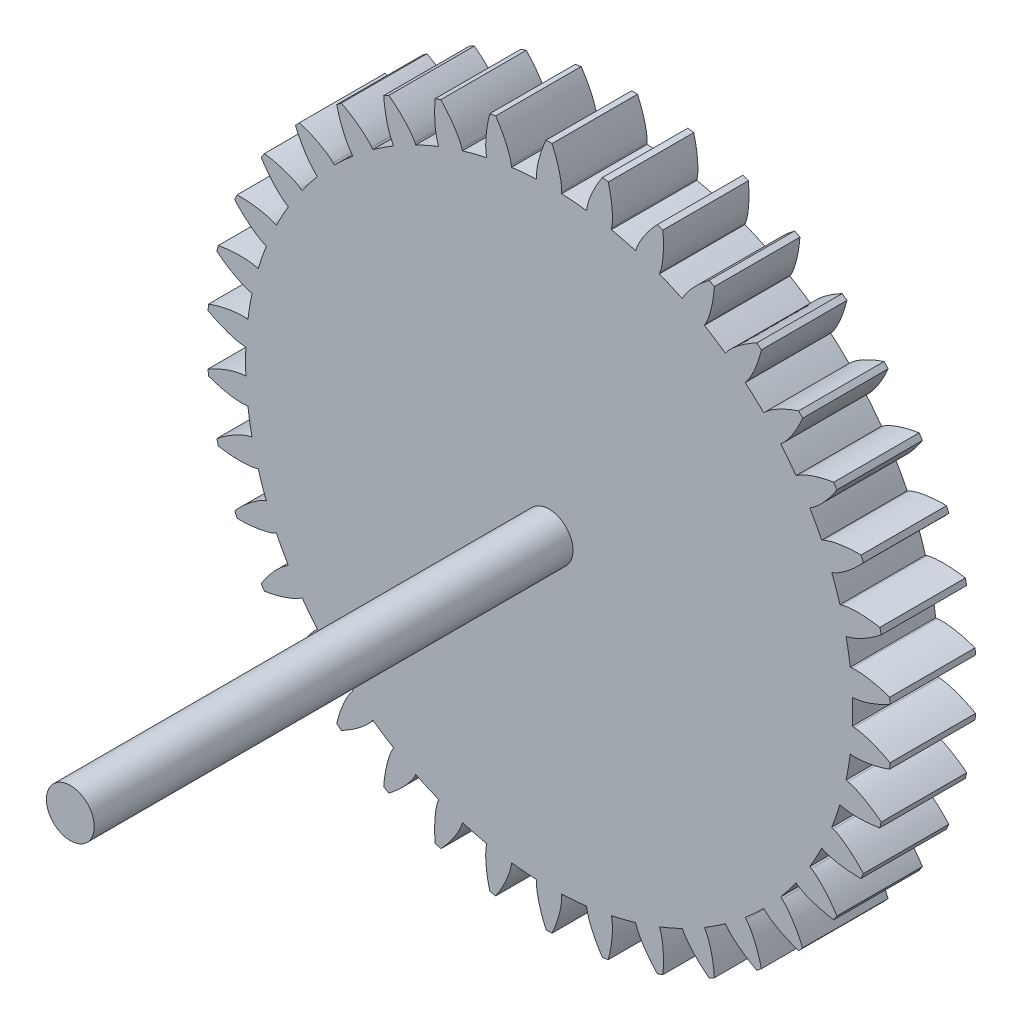
SolidWorks part; units mm, degrees
ref_plane "前视基准面" through (0, 0, 0) normal (0, 0, 1) x (1, 0, 0)
ref_plane "上视基准面" through (0, 0, 0) normal (0, 1, 0) x (1, 0, 0)
ref_plane "右视基准面" through (0, 0, 0) normal (1, 0, 0) x (0, 0, -1)
other "Configuration Table"
sketch "草图1" plane through (0, 0, 0) normal (0, 0, 1) x (1, 0, 0)
  line L0 (0, 0) -> (3, 0) construction
  line L1 (0, 0) -> (2.8978, 0.7765) construction
  line L2 (0, 0) -> (2.7305, 0.701)
  line L3 (2.8978, 0.7765) -> (2.8978, -0.7765) construction
  line L4 (0, 0) -> (2.7305, -0.701)
  circle A0 centre (0, 0) radius 4
  circle A1 centre (0, 0) radius 3 construction
  circle A2 centre (0, 0) radius 1.75
  circle A3 centre (0, 0) radius 2.8191 construction
  circle A4 centre (0, 0) radius 1.4
  spline S0 degree 4 poles (2.7305, 0.701) (2.7514, 0.7063) (2.8083, 0.7255) (2.9105, 0.779) (3.0627, 0.8875) (3.236, 1.0573) (3.4253, 1.3046) (3.6012, 1.6247) (3.742, 2.0003) (3.8364, 2.4221) (3.8779, 2.852) (3.8707, 3.2837) (3.8157, 3.7334) (3.69, 4.2802) (3.4574, 4.9086) (3.0836, 5.5918) (2.5556, 6.2772) (1.9356, 6.8796) (1.2391, 7.3923) (0.4849, 7.8122) (-0.3175, 8.1368) (-1.1468, 8.3674) (-2.0054, 8.5023) (-2.7502, 8.5427) (-3.4127, 8.5171) (-3.8849, 8.4708) (-4.3024, 8.4076) (-4.5772, 8.3558) (-4.9624, 8.2714) (-5.2496, 8.1908) (-5.5362, 8.1071) (-5.6783, 8.056) (-5.7704, 8.0254) knots 0 0 0 0 0 0.005604 0.015718 0.02996 0.048734 0.068727 0.096889 0.125051 0.153212 0.181374 0.209535 0.237696 0.271429 0.327752 0.384075 0.440398 0.496721 0.553044 0.609367 0.66569 0.722013 0.778336 0.834659 0.86282 0.890982 0.909091 0.931818 0.954545 0.977273 1 1 1 1 1 construction
  spline S1 degree 4 poles (2.7305, 0.701) (2.7514, 0.7063) (2.8083, 0.7255) (2.9105, 0.779) (3.0627, 0.8875) (3.236, 1.0573) (3.4253, 1.3046) (3.6012, 1.6247) (3.742, 2.0003) (3.8364, 2.4221) (3.8779, 2.852) (3.8707, 3.2837) (3.8157, 3.7334) (3.69, 4.2802) (3.4574, 4.9086) (3.0836, 5.5918) (2.5556, 6.2772) (1.9356, 6.8796) (1.2391, 7.3923) (0.4849, 7.8122) (-0.3175, 8.1368) (-1.1468, 8.3674) (-2.0054, 8.5023) (-2.7502, 8.5427) (-3.4127, 8.5171) (-3.8849, 8.4708) (-4.2047, 8.4224) (-4.3632, 8.395) (-4.4251, 8.3835) knots 0 0 0 0 0 0.005604 0.015718 0.02996 0.048734 0.068727 0.096889 0.125051 0.153212 0.181374 0.209535 0.237696 0.271429 0.327752 0.384075 0.440398 0.496721 0.553044 0.609367 0.66569 0.722013 0.778336 0.834659 0.86282 0.890982 0.909091 0.909091 0.909091 0.909091 0.909091
  spline S2 degree 4 poles (2.7305, -0.701) (2.7514, -0.7063) (2.8083, -0.7255) (2.9105, -0.779) (3.0627, -0.8875) (3.236, -1.0573) (3.4253, -1.3046) (3.6012, -1.6247) (3.742, -2.0003) (3.8364, -2.4221) (3.8779, -2.852) (3.8707, -3.2837) (3.8157, -3.7334) (3.69, -4.2802) (3.4574, -4.9086) (3.0836, -5.5918) (2.5556, -6.2772) (1.9356, -6.8796) (1.2391, -7.3923) (0.4849, -7.8122) (-0.3175, -8.1368) (-1.1468, -8.3674) (-2.0054, -8.5023) (-2.7502, -8.5427) (-3.4127, -8.5171) (-3.8849, -8.4708) (-4.3024, -8.4076) (-4.5772, -8.3558) (-4.9624, -8.2714) (-5.2496, -8.1908) (-5.5362, -8.1071) (-5.6783, -8.056) (-5.7704, -8.0254) knots 0 0 0 0 0 0.005604 0.015718 0.02996 0.048734 0.068727 0.096889 0.125051 0.153212 0.181374 0.209535 0.237696 0.271429 0.327752 0.384075 0.440398 0.496721 0.553044 0.609367 0.66569 0.722013 0.778336 0.834659 0.86282 0.890982 0.909091 0.931818 0.954545 0.977273 1 1 1 1 1 construction
  spline S3 degree 4 poles (2.7305, -0.701) (2.7514, -0.7063) (2.8083, -0.7255) (2.9105, -0.779) (3.0627, -0.8875) (3.236, -1.0573) (3.4253, -1.3046) (3.6012, -1.6247) (3.742, -2.0003) (3.8364, -2.4221) (3.8779, -2.852) (3.8707, -3.2837) (3.8157, -3.7334) (3.69, -4.2802) (3.4574, -4.9086) (3.0836, -5.5918) (2.5556, -6.2772) (1.9356, -6.8796) (1.2391, -7.3923) (0.4849, -7.8122) (-0.3175, -8.1368) (-1.1468, -8.3674) (-2.0054, -8.5023) (-2.7502, -8.5427) (-3.4127, -8.5171) (-3.8849, -8.4708) (-4.2047, -8.4224) (-4.3632, -8.395) (-4.4251, -8.3835) knots 0 0 0 0 0 0.005604 0.015718 0.02996 0.048734 0.068727 0.096889 0.125051 0.153212 0.181374 0.209535 0.237696 0.271429 0.327752 0.384075 0.440398 0.496721 0.553044 0.609367 0.66569 0.722013 0.778336 0.834659 0.86282 0.890982 0.909091 0.909091 0.909091 0.909091 0.909091
  point P15 (2.8978, 0)
  dimension "齿顶圆直径" = 8
  dimension "分度圆直径" = 6
  dimension "齿根圆直径" = 3.5
  dimension "基圆直径" = 5.6382
  dimension "内孔直径" = 2.8
  dimension "渐近线镜像线夹角" = 15
extrude "凸台-拉伸1" add sketch "草图1" along normal blind 5 contours A0 | A4
extrude "切除-拉伸1" cut sketch "草图1<3>" along normal through all contours A2 S3 A0 S1 region at (3.0753, 0, 0)
sketch "草图1<3>" plane through (0, 0, 0) normal (0, 0, 1) x (1, 0, 0) same geometry as "草图1"
pattern_circular "阵列(圆周)1" count 6 every 60 about axis through (0, 0, 5) along (0, 0, 1) of "切除-拉伸1"
sketch "草图2" plane through (0, 0, 5) normal (0, 0, 1) x (1, 0, 0)
  line L0 (0, 0) -> (19, 0) construction
  line L1 (0, 0) -> (17.8389, 0.7378)
  line L2 (0, 0) -> (17.8389, -0.7378)
  line L3 (17.8389, 0.7378) -> (17.8389, -0.7378) construction
  circle A0 centre (0, 0) radius 19 construction
  circle A1 centre (0, 0) radius 17.8542 construction
  circle A2 centre (0, 0) radius 17.75
  circle A3 centre (0, 0) radius 20
  circle A4 centre (0, 0) radius 1.4
  spline S0 degree 4 poles (17.8389, -0.7378) (17.8728, -0.7392) (17.9406, -0.7441) (18.0752, -0.7621) (18.3288, -0.8123) (18.6635, -0.9051) (19.1205, -1.0702) (19.658, -1.3153) (20.4669, -1.7609) (21.5195, -2.5027) (22.8507, -3.7145) (24.3091, -5.5094) (25.6114, -7.6908) (26.6766, -10.2121) (27.4216, -12.8444) (27.8645, -15.543) (28.0306, -18.4074) (27.8656, -21.9567) (27.1273, -26.1356) (25.5694, -30.8158) (23.0564, -35.6845) (20.2692, -39.5823) (17.5235, -42.6283) (15.0272, -44.9572) (12.9164, -46.6904) (10.7035, -48.2904) (8.3975, -49.7545) (5.4145, -51.4121) (1.6874, -53.1227) (-2.8247, -54.7082) (-7.1558, -55.7237) (-10.5228, -56.2445) (-12.9095, -56.489) (-14.244, -56.5948) (-15.5428, -56.66) (-16.5612, -56.6949) (-17.638, -56.7056) (-18.2041, -56.705) (-18.894, -56.6964) (-19.4423, -56.6837) (-20.126, -56.6612) (-20.9547, -56.6234) (-21.9141, -56.5638) (-23.0135, -56.4746) (-24.1084, -56.3645) (-25.2027, -56.2336) (-26.0203, -56.1199) (-26.5651, -56.0373) (-26.8369, -55.9943) knots 0 0 0 0 0 0.001401 0.002802 0.005604 0.010661 0.015718 0.022839 0.02996 0.048734 0.068727 0.096889 0.125051 0.153212 0.181374 0.209535 0.237696 0.271429 0.327752 0.384075 0.440398 0.496721 0.524883 0.553044 0.581206 0.609367 0.637529 0.66569 0.722013 0.778336 0.834659 0.84874 0.86282 0.876901 0.890982 0.900036 0.909091 0.914773 0.920455 0.926136 0.931818 0.943182 0.954545 0.965909 0.977273 0.988636 1 1 1 1 1 construction
  spline S1 degree 4 poles (17.8389, -0.7378) (17.8728, -0.7392) (17.9406, -0.7441) (18.0752, -0.7621) (18.3288, -0.8123) (18.6635, -0.9051) (19.1205, -1.0702) (19.658, -1.3153) (20.4669, -1.7609) (21.5195, -2.5027) (22.8507, -3.7145) (24.3091, -5.5094) (25.6114, -7.6908) (26.6766, -10.2121) (27.4216, -12.8444) (27.8645, -15.543) (28.0306, -18.4074) (27.8656, -21.9567) (27.1273, -26.1356) (25.5694, -30.8158) (23.0564, -35.6845) (20.2692, -39.5823) (17.5235, -42.6283) (15.0272, -44.9572) (12.9164, -46.6904) (10.7035, -48.2904) (8.3975, -49.7545) (5.4145, -51.4121) (1.6874, -53.1227) (-2.8247, -54.7082) (-7.1558, -55.7237) (-10.5228, -56.2445) (-12.9095, -56.489) (-14.244, -56.5948) (-15.5428, -56.66) (-16.5612, -56.6949) (-17.4764, -56.704) (-17.8641, -56.7049) (-18.0636, -56.7042) knots 0 0 0 0 0 0.001401 0.002802 0.005604 0.010661 0.015718 0.022839 0.02996 0.048734 0.068727 0.096889 0.125051 0.153212 0.181374 0.209535 0.237696 0.271429 0.327752 0.384075 0.440398 0.496721 0.524883 0.553044 0.581206 0.609367 0.637529 0.66569 0.722013 0.778336 0.834659 0.84874 0.86282 0.876901 0.890982 0.900036 0.909091 0.909091 0.909091 0.909091 0.909091
  spline S2 degree 4 poles (17.8389, 0.7378) (17.8728, 0.7392) (17.9406, 0.7441) (18.0752, 0.7621) (18.3288, 0.8123) (18.6635, 0.9051) (19.1205, 1.0702) (19.658, 1.3153) (20.4669, 1.7609) (21.5195, 2.5027) (22.8507, 3.7145) (24.3091, 5.5094) (25.6114, 7.6908) (26.6766, 10.2121) (27.4216, 12.8444) (27.8645, 15.543) (28.0306, 18.4074) (27.8656, 21.9567) (27.1273, 26.1356) (25.5694, 30.8158) (23.0564, 35.6845) (20.2692, 39.5823) (17.5235, 42.6283) (15.0272, 44.9572) (12.9164, 46.6904) (10.7035, 48.2904) (8.3975, 49.7545) (5.4145, 51.4121) (1.6874, 53.1227) (-2.8247, 54.7082) (-7.1558, 55.7237) (-10.5228, 56.2445) (-12.9095, 56.489) (-14.244, 56.5948) (-15.5428, 56.66) (-16.5612, 56.6949) (-17.638, 56.7056) (-18.2041, 56.705) (-18.894, 56.6964) (-19.4423, 56.6837) (-20.126, 56.6612) (-20.9547, 56.6234) (-21.9141, 56.5638) (-23.0135, 56.4746) (-24.1084, 56.3645) (-25.2027, 56.2336) (-26.0203, 56.1199) (-26.5651, 56.0373) (-26.8369, 55.9943) knots 0 0 0 0 0 0.001401 0.002802 0.005604 0.010661 0.015718 0.022839 0.02996 0.048734 0.068727 0.096889 0.125051 0.153212 0.181374 0.209535 0.237696 0.271429 0.327752 0.384075 0.440398 0.496721 0.524883 0.553044 0.581206 0.609367 0.637529 0.66569 0.722013 0.778336 0.834659 0.84874 0.86282 0.876901 0.890982 0.900036 0.909091 0.914773 0.920455 0.926136 0.931818 0.943182 0.954545 0.965909 0.977273 0.988636 1 1 1 1 1 construction
  spline S3 degree 4 poles (17.8389, 0.7378) (17.8728, 0.7392) (17.9406, 0.7441) (18.0752, 0.7621) (18.3288, 0.8123) (18.6635, 0.9051) (19.1205, 1.0702) (19.658, 1.3153) (20.4669, 1.7609) (21.5195, 2.5027) (22.8507, 3.7145) (24.3091, 5.5094) (25.6114, 7.6908) (26.6766, 10.2121) (27.4216, 12.8444) (27.8645, 15.543) (28.0306, 18.4074) (27.8656, 21.9567) (27.1273, 26.1356) (25.5694, 30.8158) (23.0564, 35.6845) (20.2692, 39.5823) (17.5235, 42.6283) (15.0272, 44.9572) (12.9164, 46.6904) (10.7035, 48.2904) (8.3975, 49.7545) (5.4145, 51.4121) (1.6874, 53.1227) (-2.8247, 54.7082) (-7.1558, 55.7237) (-10.5228, 56.2445) (-12.9095, 56.489) (-14.244, 56.5948) (-15.5428, 56.66) (-16.5612, 56.6949) (-17.4764, 56.704) (-17.8641, 56.7049) (-18.0636, 56.7042) knots 0 0 0 0 0 0.001401 0.002802 0.005604 0.010661 0.015718 0.022839 0.02996 0.048734 0.068727 0.096889 0.125051 0.153212 0.181374 0.209535 0.237696 0.271429 0.327752 0.384075 0.440398 0.496721 0.524883 0.553044 0.581206 0.609367 0.637529 0.66569 0.722013 0.778336 0.834659 0.84874 0.86282 0.876901 0.890982 0.900036 0.909091 0.909091 0.909091 0.909091 0.909091
  point P16 (17.8389, 0)
  dimension "内孔直径" = 2.8
  dimension "分度圆直径" = 38
  dimension "齿顶圆直径" = 40
  dimension "基圆直径" = 35.7083
  dimension "齿根圆直径" = 35.5
  dimension "渐开线镜像线夹角" = 2.368
extrude "凸台-拉伸2" add sketch "草图2" along normal blind 5 contours A3 | A4
extrude "切除-拉伸3" cut sketch "草图2<3>" along normal through all contours S3 L1 A2 L2 S1 A3 region at (19.0065, 0, 5)
sketch "草图2<3>" plane through (0, 0, 5) normal (0, 0, 1) x (1, 0, 0) same geometry as "草图2"
pattern_circular "阵列(圆周)2" count 38 over 360 about axis through (0, 0, 10) along (0, 0, 1) of "切除-拉伸3"
sketch "草图3" plane through (0, 0, 10) normal (0, 0, 1) x (1, 0, 0)
  circle A0 centre (0, 0) radius 1.4
  circle A1 centre (0, 0) radius 1.4 construction
  circle A2 centre (0, 0) radius 26
  circle A3 centre (0, 0) radius 1.5
  dimension "D1" = 52
  dimension "D2" = 3
extrude "凸台-拉伸3" add sketch "草图3" along normal blind 28 separate body contours A0
extrude "凸台-拉伸4" add sketch "草图3<2>" against normal blind 15 contours A0
sketch "草图3<2>" plane through (0, 0, 10) normal (0, 0, 1) x (1, 0, 0) same geometry as "草图3"
equation "\"m\"= 1'模数"
equation "\"z\"= 6'齿数"
equation "\"a\"= 20度'压力角"
equation "\"d\"= \"m\" * \"z\"'分度圆直径"
equation "\"da\"= ( \"z\" + 2 ) * \"m\"'齿顶圆直径"
equation "\"df\"= ( \"z\" - 2.5 ) * \"m\"'齿根圆直径"
equation "\"s\"= 0.5 * PI * \"m\"'分度圆齿厚"
equation "\"r\"= 0.38 * \"m\"'齿根圆角"
equation "\"B\"= 0.3 * \"d\"'齿厚"
equation "\"db\"= \"m\" * \"z\" * cos ( \"a\" )'基圆直径"
equation "\"rb\"= \"db\" / 2'基圆半径"
equation "\"齿顶圆直径@草图1\"= \"da\""
equation "\"分度圆直径@草图1\"= \"d\""
equation "\"齿根圆直径@草图1\"= \"df\""
equation "\"基圆直径@草图1\"= \"db\""
equation "\"渐近线镜像线夹角@草图1\"= 360 / 4 / \"z\""
equation "\"h\"= 5'齿轮厚度"
equation "\"ir\"= 2.8'内孔直径"
equation "\"内孔直径@草图1\"= \"ir\""
equation "\"齿轮厚@凸台-拉伸1\"= \"h\""
equation "\"齿轮夹角@阵列(圆周)1\"= 360 / \"z\""
equation "\"齿数@阵列(圆周)1\"= \"z\""
equation "\"m1\"= 1'模数"
equation "\"z1\"= 38'齿数"
equation "\"a1\"= 20度'压力角"
equation "\"d1\"= \"m1\" * \"z1\"'分度圆直径"
equation "\"da1\"= ( \"z1\" + 2 ) * \"m1\"'齿顶圆直径"
equation "\"df1\"= ( \"z1\" - 2.5 ) * \"m1\"'齿根圆直径"
equation "\"s1\"= 0.5 * PI * \"m1\"'分度圆齿厚"
equation "\"r1\"= 0.38 * \"m1\"'齿根圆角"
equation "\"B1\"= 0.3 * \"d1\"'齿厚"
equation "\"db1\"= \"m1\" * \"z1\" * cos ( \"a1\" )'基圆直径"
equation "\"rb1\"= \"db1\" / 2'基圆半径"
equation "\"分度圆直径@草图2\"= \"d1\""
equation "\"齿顶圆直径@草图2\"= \"da1\""
equation "\"基圆直径@草图2\"= \"db1\""
equation "\"齿根圆直径@草图2\"= \"df1\""
equation "\"渐开线镜像线夹角@草图2\"= 360 / 4 / \"z1\""
equation "\"内孔直径@草图2\"= \"ir\""
equation "\"二层齿轮厚@凸台-拉伸2\" = \"h1\""
equation "\"h1\"= 5'齿轮厚度"
equation "\"二层齿数@阵列(圆周)2\"= \"z1\""
